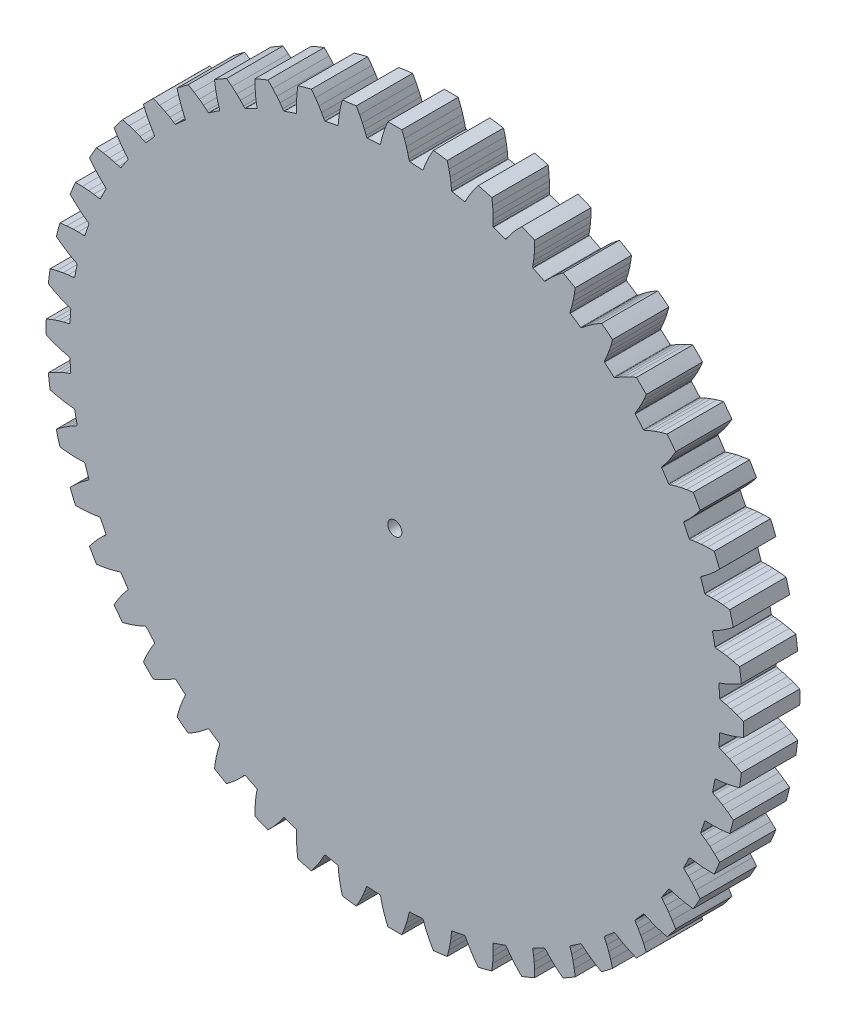
SolidWorks part; units mm, degrees
ref_plane "Front Plane" through (0, 0, 0) normal (0, 0, 1) x (1, 0, 0)
ref_plane "Top Plane" through (0, 0, 0) normal (0, 1, 0) x (1, 0, 0)
ref_plane "Right Plane" through (0, 0, 0) normal (1, 0, 0) x (0, 0, -1)
sketch "Model" plane through (0, 0, 0) normal (0, 0, 1) x (1, 0, 0)
  arc A1 (73.1624, -4.7953) -> (73.2402, -3.407) centre (0, 0) ccw
  arc A2 (73.3085, -3.2954) -> (73.2402, -3.407) centre (73.3759, -3.4133) ccw
  arc A3 (73.6777, -3.1568) -> (73.3085, -3.2954) centre (73.9216, -4.3677) ccw
  arc A4 (73.6777, -3.1568) -> (74.6891, -2.9242) centre (69.9256, 15.4758) ccw
  arc A5 (74.6891, -2.9242) -> (75.8094, -2.6049) centre (68.6862, 20.2629) ccw
  arc A6 (75.8094, -2.6049) -> (77.1527, -2.1465) centre (67.9681, 22.5684) ccw
  arc A7 (77.1527, -2.1465) -> (78.5886, -1.5721) centre (66.2481, 27.1967) ccw
  arc A8 (78.5886, -1.5721) -> (78.5886, 1.5721) centre (0, 0) ccw
  arc A9 (78.5886, 1.5721) -> (77.1527, 2.1465) centre (66.2481, -27.1967) ccw
  arc A10 (77.1527, 2.1465) -> (75.8094, 2.6049) centre (67.9681, -22.5684) ccw
  arc A11 (75.8094, 2.6049) -> (74.6891, 2.9242) centre (68.6862, -20.2629) ccw
  arc A12 (74.6891, 2.9242) -> (73.6777, 3.1568) centre (69.9256, -15.4758) ccw
  arc A13 (73.3085, 3.2954) -> (73.6777, 3.1568) centre (73.9216, 4.3677) ccw
  arc A14 (73.2402, 3.407) -> (73.3085, 3.2954) centre (73.3759, 3.4133) ccw
  arc A15 (73.2402, 3.407) -> (73.0583, 6.182) centre (0, 0) ccw
  arc A16 (73.1114, 6.3015) -> (73.0583, 6.182) centre (73.1936, 6.1934) ccw
  arc A17 (73.4595, 6.4871) -> (73.1114, 6.3015) centre (73.8593, 5.3183) ccw
  arc A18 (73.4595, 6.4871) -> (74.4318, 6.8497) centre (67.3074, 24.4705) ccw
  arc A19 (74.4318, 6.8497) -> (75.5009, 7.3125) centre (65.4538, 29.0549) ccw
  arc A20 (75.5009, 7.3125) -> (76.7728, 7.9423) centre (64.4408, 31.247) ccw
  arc A21 (76.7728, 7.9423) -> (78.1215, 8.6992) centre (62.1315, 35.6111) ccw
  arc A22 (78.1215, 8.6992) -> (77.7111, 11.8166) centre (0, 0) ccw
  arc A23 (77.7111, 11.8166) -> (76.2124, 12.1986) centre (69.2312, -18.3169) ccw
  arc A24 (76.2124, 12.1986) -> (74.8208, 12.4778) centre (70.3324, -13.5037) ccw
  arc A25 (74.8208, 12.4778) -> (73.6684, 12.6481) centre (70.7435, -11.1242) ccw
  arc A26 (73.6684, 12.6481) -> (72.6354, 12.7467) centre (71.3473, -6.2162) ccw
  arc A27 (72.2512, 12.8359) -> (72.6354, 12.7467) centre (72.7191, 13.9791) ccw
  arc A28 (72.169, 12.9376) -> (72.2512, 12.8359) centre (72.3026, 12.9615) ccw
  arc A29 (72.169, 12.9376) -> (71.6264, 15.6651) centre (0, 0) ccw
  arc A30 (71.6634, 15.7905) -> (71.6264, 15.6651) centre (71.759, 15.6941) ccw
  arc A31 (71.9843, 16.02) -> (71.6634, 15.7905) centre (72.5332, 14.9134) ccw
  arc A32 (71.9843, 16.02) -> (72.901, 16.5064) centre (63.5375, 33.0465) ccw
  arc A33 (72.901, 16.5064) -> (73.9005, 17.1047) centre (61.1014, 37.3497) ccw
  arc A34 (73.9005, 17.1047) -> (75.0793, 17.8952) centre (59.811, 39.3909) ccw
  arc A35 (75.0793, 17.8952) -> (76.3177, 18.8217) centre (56.9517, 43.4163) ccw
  arc A36 (76.3177, 18.8217) -> (75.5039, 21.8588) centre (0, 0) ccw
  arc A37 (75.5039, 21.8588) -> (73.9682, 22.0419) centre (71.0298, -9.1237) ccw
  arc A38 (73.9682, 22.0419) -> (72.5521, 22.1371) centre (71.4933, -4.208) ccw
  arc A39 (72.5521, 22.1371) -> (71.3873, 22.1556) centre (71.5902, -1.7951) ccw
  arc A40 (71.3873, 22.1556) -> (70.3502, 22.1184) centre (71.5483, 3.1496) ccw
  arc A41 (69.9576, 22.1567) -> (70.3502, 22.1184) centre (70.2723, 23.3512) ccw
  arc A42 (69.8628, 22.2468) -> (69.9576, 22.1567) centre (69.9922, 22.288) ccw
  arc A43 (69.8628, 22.2468) -> (68.9689, 24.8802) centre (0, 0) ccw
  arc A44 (68.9893, 25.0094) -> (68.9689, 24.8802) centre (69.0966, 24.9263) ccw
  arc A45 (69.2774, 25.2788) -> (68.9893, 25.0094) centre (69.9661, 24.2533) ccw
  arc A46 (69.2774, 25.2788) -> (70.1228, 25.8806) centre (58.6805, 41.0571) ccw
  arc A47 (70.1228, 25.8806) -> (71.0356, 26.6044) centre (55.7035, 45.0055) ccw
  arc A48 (71.0356, 26.6044) -> (72.1012, 27.5419) centre (54.1578, 46.8608) ccw
  arc A49 (72.1012, 27.5419) -> (73.208, 28.6221) centre (50.7976, 50.4785) ccw
  arc A50 (73.208, 28.6221) -> (72.0048, 31.527) centre (0, 0) ccw
  arc A51 (72.0048, 31.527) -> (70.4583, 31.5082) centre (71.613, 0.2256) ccw
  arc A52 (70.4583, 31.5082) -> (69.0419, 31.4176) centre (71.4309, 5.1597) ccw
  arc A53 (69.0419, 31.4176) -> (67.8847, 31.2839) centre (71.2121, 7.5646) ccw
  arc A54 (67.8847, 31.2839) -> (66.8613, 31.1117) centre (70.5251, 12.4616) ccw
  arc A55 (66.4671, 31.0985) -> (66.8613, 31.1117) centre (66.6232, 32.3238) ccw
  arc A56 (66.3614, 31.1754) -> (66.4671, 31.0985) centre (66.4843, 31.2332) ccw
  arc A57 (66.3614, 31.1754) -> (65.1314, 33.6696) centre (0, 0) ccw
  arc A58 (65.1347, 33.8003) -> (65.1314, 33.6696) centre (65.252, 33.732) ccw
  arc A59 (65.3852, 34.105) -> (65.1347, 33.8003) centre (66.2018, 33.1782) ccw
  arc A60 (65.3852, 34.105) -> (66.1448, 34.8121) centre (52.8194, 48.3652) ccw
  arc A61 (66.1448, 34.8121) -> (66.9553, 35.6488) centre (49.3526, 51.8913) ccw
  arc A62 (66.9553, 35.6488) -> (67.8894, 36.7174) centre (47.5779, 53.5289) ccw
  arc A63 (67.8894, 36.7174) -> (68.8458, 37.9328) centre (43.7742, 56.6771) ccw
  arc A64 (68.8458, 37.9328) -> (67.2737, 40.6558) centre (0, 0) ccw
  arc A65 (67.2737, 40.6558) -> (65.7429, 40.4353) centre (70.9709, 9.571) ccw
  arc A66 (65.7429, 40.4353) -> (64.3504, 40.1606) centre (70.1463, 14.4392) ccw
  arc A67 (64.3504, 40.1606) -> (63.2205, 39.877) centre (69.6155, 16.795) ccw
  arc A68 (63.2205, 39.877) -> (62.2284, 39.5727) centre (68.2952, 21.5604) ccw
  arc A69 (61.8393, 39.5081) -> (62.2284, 39.5727) centre (61.8341, 40.7434) ccw
  arc A70 (61.7244, 39.5706) -> (61.8393, 39.5081) centre (61.8387, 39.6439) ccw
  arc A71 (61.7244, 39.5706) -> (60.1794, 41.8829) centre (0, 0) ccw
  arc A72 (60.1656, 42.0129) -> (60.1794, 41.8829) centre (60.2908, 41.9605) ccw
  arc A73 (60.3742, 42.3477) -> (60.1656, 42.0129) centre (61.3049, 41.5355) ccw
  arc A74 (60.3742, 42.3477) -> (61.035, 43.1479) centre (46.0546, 54.8457) ccw
  arc A75 (61.035, 43.1479) -> (61.7294, 44.0832) centre (42.1572, 57.8892) ccw
  arc A76 (61.7294, 44.0832) -> (62.516, 45.2646) centre (40.1839, 59.2811) ccw
  arc A77 (62.516, 45.2646) -> (63.3056, 46.5945) centre (36.0019, 61.9059) ccw
  arc A78 (63.3056, 46.5945) -> (61.3915, 49.089) centre (0, 0) ccw
  arc A79 (61.3915, 49.089) -> (59.9026, 48.6705) centre (69.1145, 18.7527) ccw
  arc A80 (59.9026, 48.6705) -> (58.5579, 48.2165) centre (67.6615, 23.4716) ccw
  arc A81 (58.5579, 48.2165) -> (57.4747, 47.7878) centre (66.8277, 25.7379) ccw
  arc A82 (57.4747, 47.7878) -> (56.5307, 47.3566) centre (64.8967, 30.2902) ccw
  arc A83 (56.1534, 47.2418) -> (56.5307, 47.3566) centre (55.987, 48.4658) ccw
  arc A84 (56.0314, 47.2887) -> (56.1534, 47.2418) centre (56.1351, 47.3763) ccw
  arc A85 (56.0314, 47.2887) -> (54.1977, 49.3796) centre (0, 0) ccw
  arc A86 (54.1671, 49.5067) -> (54.1977, 49.3796) centre (54.2981, 49.471) ccw
  arc A87 (54.3302, 49.8658) -> (54.1671, 49.5067) centre (55.3589, 49.182) ccw
  arc A88 (54.3302, 49.8658) -> (54.8809, 50.7454) centre (38.5018, 60.3879) ccw
  arc A89 (54.8809, 50.7454) -> (55.4473, 51.7634) centre (34.2405, 62.8965) ccw
  arc A90 (55.4473, 51.7634) -> (56.073, 53.0374) centre (32.1024, 64.019) ccw
  arc A91 (56.073, 53.0374) -> (56.6822, 54.4589) centre (27.6135, 66.0755) ccw
  arc A92 (56.6822, 54.4589) -> (54.4589, 56.6822) centre (0, 0) ccw
  arc A93 (54.4589, 56.6822) -> (53.0374, 56.073) centre (66.0755, 27.6135) ccw
  arc A94 (53.0374, 56.073) -> (51.7634, 55.4473) centre (64.019, 32.1024) ccw
  arc A95 (51.7634, 55.4473) -> (50.7454, 54.8809) centre (62.8965, 34.2405) ccw
  arc A96 (50.7454, 54.8809) -> (49.8658, 54.3302) centre (60.3879, 38.5018) ccw
  arc A97 (49.5067, 54.1671) -> (49.8658, 54.3302) centre (49.182, 55.3589) ccw
  arc A98 (49.3796, 54.1977) -> (49.5067, 54.1671) centre (49.471, 54.2981) ccw
  arc A99 (49.3796, 54.1977) -> (47.2887, 56.0314) centre (0, 0) ccw
  arc A100 (47.2418, 56.1534) -> (47.2887, 56.0314) centre (47.3763, 56.1351) ccw
  arc A101 (47.3566, 56.5307) -> (47.2418, 56.1534) centre (48.4658, 55.987) ccw
  arc A102 (47.3566, 56.5307) -> (47.7878, 57.4747) centre (30.2902, 64.8967) ccw
  arc A103 (47.7878, 57.4747) -> (48.2165, 58.5579) centre (25.7379, 66.8277) ccw
  arc A104 (48.2165, 58.5579) -> (48.6705, 59.9026) centre (23.4716, 67.6615) ccw
  arc A105 (48.6705, 59.9026) -> (49.089, 61.3915) centre (18.7527, 69.1145) ccw
  arc A106 (49.089, 61.3915) -> (46.5945, 63.3056) centre (0, 0) ccw
  arc A107 (46.5945, 63.3056) -> (45.2646, 62.516) centre (61.9059, 36.0019) ccw
  arc A108 (45.2646, 62.516) -> (44.0832, 61.7294) centre (59.2811, 40.1839) ccw
  arc A109 (44.0832, 61.7294) -> (43.1479, 61.035) centre (57.8892, 42.1572) ccw
  arc A110 (43.1479, 61.035) -> (42.3477, 60.3742) centre (54.8457, 46.0546) ccw
  arc A111 (42.0129, 60.1656) -> (42.3477, 60.3742) centre (41.5355, 61.3049) ccw
  arc A112 (41.8829, 60.1794) -> (42.0129, 60.1656) centre (41.9605, 60.2908) ccw
  arc A113 (41.8829, 60.1794) -> (39.5706, 61.7244) centre (0, 0) ccw
  arc A114 (39.5081, 61.8393) -> (39.5706, 61.7244) centre (39.6439, 61.8387) ccw
  arc A115 (39.5727, 62.2284) -> (39.5081, 61.8393) centre (40.7434, 61.8341) ccw
  arc A116 (39.5727, 62.2284) -> (39.877, 63.2205) centre (21.5604, 68.2952) ccw
  arc A117 (39.877, 63.2205) -> (40.1606, 64.3504) centre (16.795, 69.6155) ccw
  arc A118 (40.1606, 64.3504) -> (40.4353, 65.7429) centre (14.4392, 70.1463) ccw
  arc A119 (40.4353, 65.7429) -> (40.6558, 67.2737) centre (9.571, 70.9709) ccw
  arc A120 (40.6558, 67.2737) -> (37.9328, 68.8458) centre (0, 0) ccw
  arc A121 (37.9328, 68.8458) -> (36.7174, 67.8894) centre (56.6771, 43.7742) ccw
  arc A122 (36.7174, 67.8894) -> (35.6488, 66.9553) centre (53.5289, 47.5779) ccw
  arc A123 (35.6488, 66.9553) -> (34.8121, 66.1448) centre (51.8913, 49.3526) ccw
  arc A124 (34.8121, 66.1448) -> (34.105, 65.3852) centre (48.3652, 52.8194) ccw
  arc A125 (33.8003, 65.1347) -> (34.105, 65.3852) centre (33.1782, 66.2018) ccw
  arc A126 (33.6696, 65.1314) -> (33.8003, 65.1347) centre (33.732, 65.252) ccw
  arc A127 (33.6696, 65.1314) -> (31.1754, 66.3614) centre (0, 0) ccw
  arc A128 (31.0985, 66.4671) -> (31.1754, 66.3614) centre (31.2332, 66.4843) ccw
  arc A129 (31.1117, 66.8613) -> (31.0985, 66.4671) centre (32.3238, 66.6232) ccw
  arc A130 (31.1117, 66.8613) -> (31.2839, 67.8847) centre (12.4616, 70.5251) ccw
  arc A131 (31.2839, 67.8847) -> (31.4176, 69.0419) centre (7.5646, 71.2121) ccw
  arc A132 (31.4176, 69.0419) -> (31.5082, 70.4583) centre (5.1597, 71.4309) ccw
  arc A133 (31.5082, 70.4583) -> (31.527, 72.0048) centre (0.2256, 71.613) ccw
  arc A134 (31.527, 72.0048) -> (28.6221, 73.208) centre (0, 0) ccw
  arc A135 (28.6221, 73.208) -> (27.5419, 72.1012) centre (50.4785, 50.7976) ccw
  arc A136 (27.5419, 72.1012) -> (26.6044, 71.0356) centre (46.8608, 54.1578) ccw
  arc A137 (26.6044, 71.0356) -> (25.8806, 70.1228) centre (45.0055, 55.7035) ccw
  arc A138 (25.8806, 70.1228) -> (25.2788, 69.2774) centre (41.0571, 58.6805) ccw
  arc A139 (25.0094, 68.9893) -> (25.2788, 69.2774) centre (24.2533, 69.9661) ccw
  arc A140 (24.8802, 68.9689) -> (25.0094, 68.9893) centre (24.9263, 69.0966) ccw
  arc A141 (24.8802, 68.9689) -> (22.2468, 69.8628) centre (0, 0) ccw
  arc A142 (22.1567, 69.9576) -> (22.2468, 69.8628) centre (22.288, 69.9922) ccw
  arc A143 (22.1184, 70.3502) -> (22.1567, 69.9576) centre (23.3512, 70.2723) ccw
  arc A144 (22.1184, 70.3502) -> (22.1556, 71.3873) centre (3.1496, 71.5483) ccw
  arc A145 (22.1556, 71.3873) -> (22.1371, 72.5521) centre (-1.7951, 71.5902) ccw
  arc A146 (22.1371, 72.5521) -> (22.0419, 73.9682) centre (-4.208, 71.4933) ccw
  arc A147 (22.0419, 73.9682) -> (21.8588, 75.5039) centre (-9.1237, 71.0298) ccw
  arc A148 (21.8588, 75.5039) -> (18.8217, 76.3177) centre (0, 0) ccw
  arc A149 (18.8217, 76.3177) -> (17.8952, 75.0793) centre (43.4163, 56.9517) ccw
  arc A150 (17.8952, 75.0793) -> (17.1047, 73.9005) centre (39.3909, 59.811) ccw
  arc A151 (17.1047, 73.9005) -> (16.5064, 72.901) centre (37.3497, 61.1014) ccw
  arc A152 (16.5064, 72.901) -> (16.02, 71.9843) centre (33.0465, 63.5375) ccw
  arc A153 (15.7905, 71.6634) -> (16.02, 71.9843) centre (14.9134, 72.5332) ccw
  arc A154 (15.6651, 71.6264) -> (15.7905, 71.6634) centre (15.6941, 71.759) ccw
  arc A155 (15.6651, 71.6264) -> (12.9376, 72.169) centre (0, 0) ccw
  arc A156 (12.8359, 72.2512) -> (12.9376, 72.169) centre (12.9615, 72.3026) ccw
  arc A157 (12.7467, 72.6354) -> (12.8359, 72.2512) centre (13.9791, 72.7191) ccw
  arc A158 (12.7467, 72.6354) -> (12.6481, 73.6684) centre (-6.2162, 71.3473) ccw
  arc A159 (12.6481, 73.6684) -> (12.4778, 74.8208) centre (-11.1242, 70.7435) ccw
  arc A160 (12.4778, 74.8208) -> (12.1986, 76.2124) centre (-13.5037, 70.3324) ccw
  arc A161 (12.1986, 76.2124) -> (11.8166, 77.7111) centre (-18.3169, 69.2312) ccw
  arc A162 (11.8166, 77.7111) -> (8.6992, 78.1215) centre (0, 0) ccw
  arc A163 (8.6992, 78.1215) -> (7.9423, 76.7728) centre (35.6111, 62.1315) ccw
  arc A164 (7.9423, 76.7728) -> (7.3125, 75.5009) centre (31.247, 64.4408) ccw
  arc A165 (7.3125, 75.5009) -> (6.8497, 74.4318) centre (29.0549, 65.4538) ccw
  arc A166 (6.8497, 74.4318) -> (6.4871, 73.4595) centre (24.4705, 67.3074) ccw
  arc A167 (6.3015, 73.1114) -> (6.4871, 73.4595) centre (5.3183, 73.8593) ccw
  arc A168 (6.182, 73.0583) -> (6.3015, 73.1114) centre (6.1934, 73.1936) ccw
  arc A169 (6.182, 73.0583) -> (3.407, 73.2402) centre (0, 0) ccw
  arc A170 (3.2954, 73.3085) -> (3.407, 73.2402) centre (3.4133, 73.3759) ccw
  arc A171 (3.1568, 73.6777) -> (3.2954, 73.3085) centre (4.3677, 73.9216) ccw
  arc A172 (3.1568, 73.6777) -> (2.9242, 74.6891) centre (-15.4758, 69.9256) ccw
  arc A173 (2.9242, 74.6891) -> (2.6049, 75.8094) centre (-20.2629, 68.6862) ccw
  arc A174 (2.6049, 75.8094) -> (2.1465, 77.1527) centre (-22.5684, 67.9681) ccw
  arc A175 (2.1465, 77.1527) -> (1.5721, 78.5886) centre (-27.1967, 66.2481) ccw
  arc A176 (1.5721, 78.5886) -> (-1.5721, 78.5886) centre (0, 0) ccw
  arc A177 (-1.5721, 78.5886) -> (-2.1465, 77.1527) centre (27.1967, 66.2481) ccw
  arc A178 (-2.1465, 77.1527) -> (-2.6049, 75.8094) centre (22.5684, 67.9681) ccw
  arc A179 (-2.6049, 75.8094) -> (-2.9242, 74.6891) centre (20.2629, 68.6862) ccw
  arc A180 (-2.9242, 74.6891) -> (-3.1568, 73.6777) centre (15.4758, 69.9256) ccw
  arc A181 (-3.2954, 73.3085) -> (-3.1568, 73.6777) centre (-4.3677, 73.9216) ccw
  arc A182 (-3.407, 73.2402) -> (-3.2954, 73.3085) centre (-3.4133, 73.3759) ccw
  arc A183 (-3.407, 73.2402) -> (-6.182, 73.0583) centre (0, 0) ccw
  arc A184 (-6.3015, 73.1114) -> (-6.182, 73.0583) centre (-6.1934, 73.1936) ccw
  arc A185 (-6.4871, 73.4595) -> (-6.3015, 73.1114) centre (-5.3183, 73.8593) ccw
  arc A186 (-6.4871, 73.4595) -> (-6.8497, 74.4318) centre (-24.4705, 67.3074) ccw
  arc A187 (-6.8497, 74.4318) -> (-7.3125, 75.5009) centre (-29.0549, 65.4538) ccw
  arc A188 (-7.3125, 75.5009) -> (-7.9423, 76.7728) centre (-31.247, 64.4408) ccw
  arc A189 (-7.9423, 76.7728) -> (-8.6992, 78.1215) centre (-35.6111, 62.1315) ccw
  arc A190 (-8.6992, 78.1215) -> (-11.8166, 77.7111) centre (0, 0) ccw
  arc A191 (-11.8166, 77.7111) -> (-12.1986, 76.2124) centre (18.3169, 69.2312) ccw
  arc A192 (-12.1986, 76.2124) -> (-12.4778, 74.8208) centre (13.5037, 70.3324) ccw
  arc A193 (-12.4778, 74.8208) -> (-12.6481, 73.6684) centre (11.1242, 70.7435) ccw
  arc A194 (-12.6481, 73.6684) -> (-12.7467, 72.6354) centre (6.2162, 71.3473) ccw
  arc A195 (-12.8359, 72.2512) -> (-12.7467, 72.6354) centre (-13.9791, 72.7191) ccw
  arc A196 (-12.9376, 72.169) -> (-12.8359, 72.2512) centre (-12.9615, 72.3026) ccw
  arc A197 (-12.9376, 72.169) -> (-15.6651, 71.6264) centre (0, 0) ccw
  arc A198 (-15.7905, 71.6634) -> (-15.6651, 71.6264) centre (-15.6941, 71.759) ccw
  arc A199 (-16.02, 71.9843) -> (-15.7905, 71.6634) centre (-14.9134, 72.5332) ccw
  arc A200 (-16.02, 71.9843) -> (-16.5064, 72.901) centre (-33.0465, 63.5375) ccw
  arc A201 (-16.5064, 72.901) -> (-17.1047, 73.9005) centre (-37.3497, 61.1014) ccw
  arc A202 (-17.1047, 73.9005) -> (-17.8952, 75.0793) centre (-39.3909, 59.811) ccw
  arc A203 (-17.8952, 75.0793) -> (-18.8217, 76.3177) centre (-43.4163, 56.9517) ccw
  arc A204 (-18.8217, 76.3177) -> (-21.8588, 75.5039) centre (0, 0) ccw
  arc A205 (-21.8588, 75.5039) -> (-22.0419, 73.9682) centre (9.1237, 71.0298) ccw
  arc A206 (-22.0419, 73.9682) -> (-22.1371, 72.5521) centre (4.208, 71.4933) ccw
  arc A207 (-22.1371, 72.5521) -> (-22.1556, 71.3873) centre (1.7951, 71.5902) ccw
  arc A208 (-22.1556, 71.3873) -> (-22.1184, 70.3502) centre (-3.1496, 71.5483) ccw
  arc A209 (-22.1567, 69.9576) -> (-22.1184, 70.3502) centre (-23.3512, 70.2723) ccw
  arc A210 (-22.2468, 69.8628) -> (-22.1567, 69.9576) centre (-22.288, 69.9922) ccw
  arc A211 (-22.2468, 69.8628) -> (-24.8802, 68.9689) centre (0, 0) ccw
  arc A212 (-25.0094, 68.9893) -> (-24.8802, 68.9689) centre (-24.9263, 69.0966) ccw
  arc A213 (-25.2788, 69.2774) -> (-25.0094, 68.9893) centre (-24.2533, 69.9661) ccw
  arc A214 (-25.2788, 69.2774) -> (-25.8806, 70.1228) centre (-41.0571, 58.6805) ccw
  arc A215 (-25.8806, 70.1228) -> (-26.6044, 71.0356) centre (-45.0055, 55.7035) ccw
  arc A216 (-26.6044, 71.0356) -> (-27.5419, 72.1012) centre (-46.8608, 54.1578) ccw
  arc A217 (-27.5419, 72.1012) -> (-28.6221, 73.208) centre (-50.4785, 50.7976) ccw
  arc A218 (-28.6221, 73.208) -> (-31.527, 72.0048) centre (0, 0) ccw
  arc A219 (-31.527, 72.0048) -> (-31.5082, 70.4583) centre (-0.2256, 71.613) ccw
  arc A220 (-31.5082, 70.4583) -> (-31.4176, 69.0419) centre (-5.1597, 71.4309) ccw
  arc A221 (-31.4176, 69.0419) -> (-31.2839, 67.8847) centre (-7.5646, 71.2121) ccw
  arc A222 (-31.2839, 67.8847) -> (-31.1117, 66.8613) centre (-12.4616, 70.5251) ccw
  arc A223 (-31.0985, 66.4671) -> (-31.1117, 66.8613) centre (-32.3238, 66.6232) ccw
  arc A224 (-31.1754, 66.3614) -> (-31.0985, 66.4671) centre (-31.2332, 66.4843) ccw
  arc A225 (-31.1754, 66.3614) -> (-33.6696, 65.1314) centre (0, 0) ccw
  arc A226 (-33.8003, 65.1347) -> (-33.6696, 65.1314) centre (-33.732, 65.252) ccw
  arc A227 (-34.105, 65.3852) -> (-33.8003, 65.1347) centre (-33.1782, 66.2018) ccw
  arc A228 (-34.105, 65.3852) -> (-34.8121, 66.1448) centre (-48.3652, 52.8194) ccw
  arc A229 (-34.8121, 66.1448) -> (-35.6488, 66.9553) centre (-51.8913, 49.3526) ccw
  arc A230 (-35.6488, 66.9553) -> (-36.7174, 67.8894) centre (-53.5289, 47.5779) ccw
  arc A231 (-36.7174, 67.8894) -> (-37.9328, 68.8458) centre (-56.6771, 43.7742) ccw
  arc A232 (-37.9328, 68.8458) -> (-40.6558, 67.2737) centre (0, 0) ccw
  arc A233 (-40.6558, 67.2737) -> (-40.4353, 65.7429) centre (-9.571, 70.9709) ccw
  arc A234 (-40.4353, 65.7429) -> (-40.1606, 64.3504) centre (-14.4392, 70.1463) ccw
  arc A235 (-40.1606, 64.3504) -> (-39.877, 63.2205) centre (-16.795, 69.6155) ccw
  arc A236 (-39.877, 63.2205) -> (-39.5727, 62.2284) centre (-21.5604, 68.2952) ccw
  arc A237 (-39.5081, 61.8393) -> (-39.5727, 62.2284) centre (-40.7434, 61.8341) ccw
  arc A238 (-39.5706, 61.7244) -> (-39.5081, 61.8393) centre (-39.6439, 61.8387) ccw
  arc A239 (-39.5706, 61.7244) -> (-41.8829, 60.1794) centre (0, 0) ccw
  arc A240 (-42.0129, 60.1656) -> (-41.8829, 60.1794) centre (-41.9605, 60.2908) ccw
  arc A241 (-42.3477, 60.3742) -> (-42.0129, 60.1656) centre (-41.5355, 61.3049) ccw
  arc A242 (-42.3477, 60.3742) -> (-43.1479, 61.035) centre (-54.8457, 46.0546) ccw
  arc A243 (-43.1479, 61.035) -> (-44.0832, 61.7294) centre (-57.8892, 42.1572) ccw
  arc A244 (-44.0832, 61.7294) -> (-45.2646, 62.516) centre (-59.2811, 40.1839) ccw
  arc A245 (-45.2646, 62.516) -> (-46.5945, 63.3056) centre (-61.9059, 36.0019) ccw
  arc A246 (-46.5945, 63.3056) -> (-49.089, 61.3915) centre (0, 0) ccw
  arc A247 (-49.089, 61.3915) -> (-48.6705, 59.9026) centre (-18.7527, 69.1145) ccw
  arc A248 (-48.6705, 59.9026) -> (-48.2165, 58.5579) centre (-23.4716, 67.6615) ccw
  arc A249 (-48.2165, 58.5579) -> (-47.7878, 57.4747) centre (-25.7379, 66.8277) ccw
  arc A250 (-47.7878, 57.4747) -> (-47.3566, 56.5307) centre (-30.2902, 64.8967) ccw
  arc A251 (-47.2418, 56.1534) -> (-47.3566, 56.5307) centre (-48.4658, 55.987) ccw
  arc A252 (-47.2887, 56.0314) -> (-47.2418, 56.1534) centre (-47.3763, 56.1351) ccw
  arc A253 (-47.2887, 56.0314) -> (-49.3796, 54.1977) centre (0, 0) ccw
  arc A254 (-49.5067, 54.1671) -> (-49.3796, 54.1977) centre (-49.471, 54.2981) ccw
  arc A255 (-49.8658, 54.3302) -> (-49.5067, 54.1671) centre (-49.182, 55.3589) ccw
  arc A256 (-49.8658, 54.3302) -> (-50.7454, 54.8809) centre (-60.3879, 38.5018) ccw
  arc A257 (-50.7454, 54.8809) -> (-51.7634, 55.4473) centre (-62.8965, 34.2405) ccw
  arc A258 (-51.7634, 55.4473) -> (-53.0374, 56.073) centre (-64.019, 32.1024) ccw
  arc A259 (-53.0374, 56.073) -> (-54.4589, 56.6822) centre (-66.0755, 27.6135) ccw
  arc A260 (-54.4589, 56.6822) -> (-56.6822, 54.4589) centre (0, 0) ccw
  arc A261 (-56.6822, 54.4589) -> (-56.073, 53.0374) centre (-27.6135, 66.0755) ccw
  arc A262 (-56.073, 53.0374) -> (-55.4473, 51.7634) centre (-32.1024, 64.019) ccw
  arc A263 (-55.4473, 51.7634) -> (-54.8809, 50.7454) centre (-34.2405, 62.8965) ccw
  arc A264 (-54.8809, 50.7454) -> (-54.3302, 49.8658) centre (-38.5018, 60.3879) ccw
  arc A265 (-54.1671, 49.5067) -> (-54.3302, 49.8658) centre (-55.3589, 49.182) ccw
  arc A266 (-54.1977, 49.3796) -> (-54.1671, 49.5067) centre (-54.2981, 49.471) ccw
  arc A267 (-54.1977, 49.3796) -> (-56.0314, 47.2887) centre (0, 0) ccw
  arc A268 (-56.1534, 47.2418) -> (-56.0314, 47.2887) centre (-56.1351, 47.3763) ccw
  arc A269 (-56.5307, 47.3566) -> (-56.1534, 47.2418) centre (-55.987, 48.4658) ccw
  arc A270 (-56.5307, 47.3566) -> (-57.4747, 47.7878) centre (-64.8967, 30.2902) ccw
  arc A271 (-57.4747, 47.7878) -> (-58.5579, 48.2165) centre (-66.8277, 25.7379) ccw
  arc A272 (-58.5579, 48.2165) -> (-59.9026, 48.6705) centre (-67.6615, 23.4716) ccw
  arc A273 (-59.9026, 48.6705) -> (-61.3915, 49.089) centre (-69.1145, 18.7527) ccw
  arc A274 (-61.3915, 49.089) -> (-63.3056, 46.5945) centre (0, 0) ccw
  arc A275 (-63.3056, 46.5945) -> (-62.516, 45.2646) centre (-36.0019, 61.9059) ccw
  arc A276 (-62.516, 45.2646) -> (-61.7294, 44.0832) centre (-40.1839, 59.2811) ccw
  arc A277 (-61.7294, 44.0832) -> (-61.035, 43.1479) centre (-42.1572, 57.8892) ccw
  arc A278 (-61.035, 43.1479) -> (-60.3742, 42.3477) centre (-46.0546, 54.8457) ccw
  arc A279 (-60.1656, 42.0129) -> (-60.3742, 42.3477) centre (-61.3049, 41.5355) ccw
  arc A280 (-60.1794, 41.8829) -> (-60.1656, 42.0129) centre (-60.2908, 41.9605) ccw
  arc A281 (-60.1794, 41.8829) -> (-61.7244, 39.5706) centre (0, 0) ccw
  arc A282 (-61.8393, 39.5081) -> (-61.7244, 39.5706) centre (-61.8387, 39.6439) ccw
  arc A283 (-62.2284, 39.5727) -> (-61.8393, 39.5081) centre (-61.8341, 40.7434) ccw
  arc A284 (-62.2284, 39.5727) -> (-63.2205, 39.877) centre (-68.2952, 21.5604) ccw
  arc A285 (-63.2205, 39.877) -> (-64.3504, 40.1606) centre (-69.6155, 16.795) ccw
  arc A286 (-64.3504, 40.1606) -> (-65.7429, 40.4353) centre (-70.1463, 14.4392) ccw
  arc A287 (-65.7429, 40.4353) -> (-67.2737, 40.6558) centre (-70.9709, 9.571) ccw
  arc A288 (-67.2737, 40.6558) -> (-68.8458, 37.9328) centre (0, 0) ccw
  arc A289 (-68.8458, 37.9328) -> (-67.8894, 36.7174) centre (-43.7742, 56.6771) ccw
  arc A290 (-67.8894, 36.7174) -> (-66.9553, 35.6488) centre (-47.5779, 53.5289) ccw
  arc A291 (-66.9553, 35.6488) -> (-66.1448, 34.8121) centre (-49.3526, 51.8913) ccw
  arc A292 (-66.1448, 34.8121) -> (-65.3852, 34.105) centre (-52.8194, 48.3652) ccw
  arc A293 (-65.1347, 33.8003) -> (-65.3852, 34.105) centre (-66.2018, 33.1782) ccw
  arc A294 (-65.1314, 33.6696) -> (-65.1347, 33.8003) centre (-65.252, 33.732) ccw
  arc A295 (-65.1314, 33.6696) -> (-66.3614, 31.1754) centre (0, 0) ccw
  arc A296 (-66.4671, 31.0985) -> (-66.3614, 31.1754) centre (-66.4843, 31.2332) ccw
  arc A297 (-66.8613, 31.1117) -> (-66.4671, 31.0985) centre (-66.6232, 32.3238) ccw
  arc A298 (-66.8613, 31.1117) -> (-67.8847, 31.2839) centre (-70.5251, 12.4616) ccw
  arc A299 (-67.8847, 31.2839) -> (-69.0419, 31.4176) centre (-71.2121, 7.5646) ccw
  arc A300 (-69.0419, 31.4176) -> (-70.4583, 31.5082) centre (-71.4309, 5.1597) ccw
  arc A301 (-70.4583, 31.5082) -> (-72.0048, 31.527) centre (-71.613, 0.2256) ccw
  arc A302 (-72.0048, 31.527) -> (-73.208, 28.6221) centre (0, 0) ccw
  arc A303 (-73.208, 28.6221) -> (-72.1012, 27.5419) centre (-50.7976, 50.4785) ccw
  arc A304 (-72.1012, 27.5419) -> (-71.0356, 26.6044) centre (-54.1578, 46.8608) ccw
  arc A305 (-71.0356, 26.6044) -> (-70.1228, 25.8806) centre (-55.7035, 45.0055) ccw
  arc A306 (-70.1228, 25.8806) -> (-69.2774, 25.2788) centre (-58.6805, 41.0571) ccw
  arc A307 (-68.9893, 25.0094) -> (-69.2774, 25.2788) centre (-69.9661, 24.2533) ccw
  arc A308 (-68.9689, 24.8802) -> (-68.9893, 25.0094) centre (-69.0966, 24.9263) ccw
  arc A309 (-68.9689, 24.8802) -> (-69.8628, 22.2468) centre (0, 0) ccw
  arc A310 (-69.9576, 22.1567) -> (-69.8628, 22.2468) centre (-69.9922, 22.288) ccw
  arc A311 (-70.3502, 22.1184) -> (-69.9576, 22.1567) centre (-70.2723, 23.3512) ccw
  arc A312 (-70.3502, 22.1184) -> (-71.3873, 22.1556) centre (-71.5483, 3.1496) ccw
  arc A313 (-71.3873, 22.1556) -> (-72.5521, 22.1371) centre (-71.5902, -1.7951) ccw
  arc A314 (-72.5521, 22.1371) -> (-73.9682, 22.0419) centre (-71.4933, -4.208) ccw
  arc A315 (-73.9682, 22.0419) -> (-75.5039, 21.8588) centre (-71.0298, -9.1237) ccw
  arc A316 (-75.5039, 21.8588) -> (-76.3177, 18.8217) centre (0, 0) ccw
  arc A317 (-76.3177, 18.8217) -> (-75.0793, 17.8952) centre (-56.9517, 43.4163) ccw
  arc A318 (-75.0793, 17.8952) -> (-73.9005, 17.1047) centre (-59.811, 39.3909) ccw
  arc A319 (-73.9005, 17.1047) -> (-72.901, 16.5064) centre (-61.1014, 37.3497) ccw
  arc A320 (-72.901, 16.5064) -> (-71.9843, 16.02) centre (-63.5375, 33.0465) ccw
  arc A321 (-71.6634, 15.7905) -> (-71.9843, 16.02) centre (-72.5332, 14.9134) ccw
  arc A322 (-71.6264, 15.6651) -> (-71.6634, 15.7905) centre (-71.759, 15.6941) ccw
  arc A323 (-71.6264, 15.6651) -> (-72.169, 12.9376) centre (0, 0) ccw
  arc A324 (-72.2512, 12.8359) -> (-72.169, 12.9376) centre (-72.3026, 12.9615) ccw
  arc A325 (-72.6354, 12.7467) -> (-72.2512, 12.8359) centre (-72.7191, 13.9791) ccw
  arc A326 (-72.6354, 12.7467) -> (-73.6684, 12.6481) centre (-71.3473, -6.2162) ccw
  arc A327 (-73.6684, 12.6481) -> (-74.8208, 12.4778) centre (-70.7435, -11.1242) ccw
  arc A328 (-74.8208, 12.4778) -> (-76.2124, 12.1986) centre (-70.3324, -13.5037) ccw
  arc A329 (-76.2124, 12.1986) -> (-77.7111, 11.8166) centre (-69.2312, -18.3169) ccw
  arc A330 (-77.7111, 11.8166) -> (-78.1215, 8.6992) centre (0, 0) ccw
  arc A331 (-78.1215, 8.6992) -> (-76.7728, 7.9423) centre (-62.1315, 35.6111) ccw
  arc A332 (-76.7728, 7.9423) -> (-75.5009, 7.3125) centre (-64.4408, 31.247) ccw
  arc A333 (-75.5009, 7.3125) -> (-74.4318, 6.8497) centre (-65.4538, 29.0549) ccw
  arc A334 (-74.4318, 6.8497) -> (-73.4595, 6.4871) centre (-67.3074, 24.4705) ccw
  arc A335 (-73.1114, 6.3015) -> (-73.4595, 6.4871) centre (-73.8593, 5.3183) ccw
  arc A336 (-73.0583, 6.182) -> (-73.1114, 6.3015) centre (-73.1936, 6.1934) ccw
  arc A337 (-73.0583, 6.182) -> (-73.2402, 3.407) centre (0, 0) ccw
  arc A338 (-73.3085, 3.2954) -> (-73.2402, 3.407) centre (-73.3759, 3.4133) ccw
  arc A339 (-73.6777, 3.1568) -> (-73.3085, 3.2954) centre (-73.9216, 4.3677) ccw
  arc A340 (-73.6777, 3.1568) -> (-74.6891, 2.9242) centre (-69.9256, -15.4758) ccw
  arc A341 (-74.6891, 2.9242) -> (-75.8094, 2.6049) centre (-68.6862, -20.2629) ccw
  arc A342 (-75.8094, 2.6049) -> (-77.1527, 2.1465) centre (-67.9681, -22.5684) ccw
  arc A343 (-77.1527, 2.1465) -> (-78.5886, 1.5721) centre (-66.2481, -27.1967) ccw
  arc A344 (-78.5886, 1.5721) -> (-78.5886, -1.5721) centre (0, 0) ccw
  arc A345 (-78.5886, -1.5721) -> (-77.1527, -2.1465) centre (-66.2481, 27.1967) ccw
  arc A346 (-77.1527, -2.1465) -> (-75.8094, -2.6049) centre (-67.9681, 22.5684) ccw
  arc A347 (-75.8094, -2.6049) -> (-74.6891, -2.9242) centre (-68.6862, 20.2629) ccw
  arc A348 (-74.6891, -2.9242) -> (-73.6777, -3.1568) centre (-69.9256, 15.4758) ccw
  arc A349 (-73.3085, -3.2954) -> (-73.6777, -3.1568) centre (-73.9216, -4.3677) ccw
  arc A350 (-73.2402, -3.407) -> (-73.3085, -3.2954) centre (-73.3759, -3.4133) ccw
  arc A351 (-73.2402, -3.407) -> (-73.0583, -6.182) centre (0, 0) ccw
  arc A352 (-73.1114, -6.3015) -> (-73.0583, -6.182) centre (-73.1936, -6.1934) ccw
  arc A353 (-73.4595, -6.4871) -> (-73.1114, -6.3015) centre (-73.8593, -5.3183) ccw
  arc A354 (-73.4595, -6.4871) -> (-74.4318, -6.8497) centre (-67.3074, -24.4705) ccw
  arc A355 (-74.4318, -6.8497) -> (-75.5009, -7.3125) centre (-65.4538, -29.0549) ccw
  arc A356 (-75.5009, -7.3125) -> (-76.7728, -7.9423) centre (-64.4408, -31.247) ccw
  arc A357 (-76.7728, -7.9423) -> (-78.1215, -8.6992) centre (-62.1315, -35.6111) ccw
  arc A358 (-78.1215, -8.6992) -> (-77.7111, -11.8166) centre (0, 0) ccw
  arc A359 (-77.7111, -11.8166) -> (-76.2124, -12.1986) centre (-69.2312, 18.3169) ccw
  arc A360 (-76.2124, -12.1986) -> (-74.8208, -12.4778) centre (-70.3324, 13.5037) ccw
  arc A361 (-74.8208, -12.4778) -> (-73.6684, -12.6481) centre (-70.7435, 11.1242) ccw
  arc A362 (-73.6684, -12.6481) -> (-72.6354, -12.7467) centre (-71.3473, 6.2162) ccw
  arc A363 (-72.2512, -12.8359) -> (-72.6354, -12.7467) centre (-72.7191, -13.9791) ccw
  arc A364 (-72.169, -12.9376) -> (-72.2512, -12.8359) centre (-72.3026, -12.9615) ccw
  arc A365 (-72.169, -12.9376) -> (-71.6264, -15.6651) centre (0, 0) ccw
  arc A366 (-71.6634, -15.7905) -> (-71.6264, -15.6651) centre (-71.759, -15.6941) ccw
  arc A367 (-71.9843, -16.02) -> (-71.6634, -15.7905) centre (-72.5332, -14.9134) ccw
  arc A368 (-71.9843, -16.02) -> (-72.901, -16.5064) centre (-63.5375, -33.0465) ccw
  arc A369 (-72.901, -16.5064) -> (-73.9005, -17.1047) centre (-61.1014, -37.3497) ccw
  arc A370 (-73.9005, -17.1047) -> (-75.0793, -17.8952) centre (-59.811, -39.3909) ccw
  arc A371 (-75.0793, -17.8952) -> (-76.3177, -18.8217) centre (-56.9517, -43.4163) ccw
  arc A372 (-76.3177, -18.8217) -> (-75.5039, -21.8588) centre (0, 0) ccw
  arc A373 (-75.5039, -21.8588) -> (-73.9682, -22.0419) centre (-71.0298, 9.1237) ccw
  arc A374 (-73.9682, -22.0419) -> (-72.5521, -22.1371) centre (-71.4933, 4.208) ccw
  arc A375 (-72.5521, -22.1371) -> (-71.3873, -22.1556) centre (-71.5902, 1.7951) ccw
  arc A376 (-71.3873, -22.1556) -> (-70.3502, -22.1184) centre (-71.5483, -3.1496) ccw
  arc A377 (-69.9576, -22.1567) -> (-70.3502, -22.1184) centre (-70.2723, -23.3512) ccw
  arc A378 (-69.8628, -22.2468) -> (-69.9576, -22.1567) centre (-69.9922, -22.288) ccw
  arc A379 (-69.8628, -22.2468) -> (-68.9689, -24.8802) centre (0, 0) ccw
  arc A380 (-68.9893, -25.0094) -> (-68.9689, -24.8802) centre (-69.0966, -24.9263) ccw
  arc A381 (-69.2774, -25.2788) -> (-68.9893, -25.0094) centre (-69.9661, -24.2533) ccw
  arc A382 (-69.2774, -25.2788) -> (-70.1228, -25.8806) centre (-58.6805, -41.0571) ccw
  arc A383 (-70.1228, -25.8806) -> (-71.0356, -26.6044) centre (-55.7035, -45.0055) ccw
  arc A384 (-71.0356, -26.6044) -> (-72.1012, -27.5419) centre (-54.1578, -46.8608) ccw
  arc A385 (-72.1012, -27.5419) -> (-73.208, -28.6221) centre (-50.7976, -50.4785) ccw
  arc A386 (-73.208, -28.6221) -> (-72.0048, -31.527) centre (0, 0) ccw
  arc A387 (-72.0048, -31.527) -> (-70.4583, -31.5082) centre (-71.613, -0.2256) ccw
  arc A388 (-70.4583, -31.5082) -> (-69.0419, -31.4176) centre (-71.4309, -5.1597) ccw
  arc A389 (-69.0419, -31.4176) -> (-67.8847, -31.2839) centre (-71.2121, -7.5646) ccw
  arc A390 (-67.8847, -31.2839) -> (-66.8613, -31.1117) centre (-70.5251, -12.4616) ccw
  arc A391 (-66.4671, -31.0985) -> (-66.8613, -31.1117) centre (-66.6232, -32.3238) ccw
  arc A392 (-66.3614, -31.1754) -> (-66.4671, -31.0985) centre (-66.4843, -31.2332) ccw
  arc A393 (-66.3614, -31.1754) -> (-65.1314, -33.6696) centre (0, 0) ccw
  arc A394 (-65.1347, -33.8003) -> (-65.1314, -33.6696) centre (-65.252, -33.732) ccw
  arc A395 (-65.3852, -34.105) -> (-65.1347, -33.8003) centre (-66.2018, -33.1782) ccw
  arc A396 (-65.3852, -34.105) -> (-66.1448, -34.8121) centre (-52.8194, -48.3652) ccw
  arc A397 (-66.1448, -34.8121) -> (-66.9553, -35.6488) centre (-49.3526, -51.8913) ccw
  arc A398 (-66.9553, -35.6488) -> (-67.8894, -36.7174) centre (-47.5779, -53.5289) ccw
  arc A399 (-67.8894, -36.7174) -> (-68.8458, -37.9328) centre (-43.7742, -56.6771) ccw
  arc A400 (-68.8458, -37.9328) -> (-67.2737, -40.6558) centre (0, 0) ccw
  arc A401 (-67.2737, -40.6558) -> (-65.7429, -40.4353) centre (-70.9709, -9.571) ccw
  arc A402 (-65.7429, -40.4353) -> (-64.3504, -40.1606) centre (-70.1463, -14.4392) ccw
  arc A403 (-64.3504, -40.1606) -> (-63.2205, -39.877) centre (-69.6155, -16.795) ccw
  arc A404 (-63.2205, -39.877) -> (-62.2284, -39.5727) centre (-68.2952, -21.5604) ccw
  arc A405 (-61.8393, -39.5081) -> (-62.2284, -39.5727) centre (-61.8341, -40.7434) ccw
  arc A406 (-61.7244, -39.5706) -> (-61.8393, -39.5081) centre (-61.8387, -39.6439) ccw
  arc A407 (-61.7244, -39.5706) -> (-60.1794, -41.8829) centre (0, 0) ccw
  arc A408 (-60.1656, -42.0129) -> (-60.1794, -41.8829) centre (-60.2908, -41.9605) ccw
  arc A409 (-60.3742, -42.3477) -> (-60.1656, -42.0129) centre (-61.3049, -41.5355) ccw
  arc A410 (-60.3742, -42.3477) -> (-61.035, -43.1479) centre (-46.0546, -54.8457) ccw
  arc A411 (-61.035, -43.1479) -> (-61.7294, -44.0832) centre (-42.1572, -57.8892) ccw
  arc A412 (-61.7294, -44.0832) -> (-62.516, -45.2646) centre (-40.1839, -59.2811) ccw
  arc A413 (-62.516, -45.2646) -> (-63.3056, -46.5945) centre (-36.0019, -61.9059) ccw
  arc A414 (-63.3056, -46.5945) -> (-61.3915, -49.089) centre (0, 0) ccw
  arc A415 (-61.3915, -49.089) -> (-59.9026, -48.6705) centre (-69.1145, -18.7527) ccw
  arc A416 (-59.9026, -48.6705) -> (-58.5579, -48.2165) centre (-67.6615, -23.4716) ccw
  arc A417 (-58.5579, -48.2165) -> (-57.4747, -47.7878) centre (-66.8277, -25.7379) ccw
  arc A418 (-57.4747, -47.7878) -> (-56.5307, -47.3566) centre (-64.8967, -30.2902) ccw
  arc A419 (-56.1534, -47.2418) -> (-56.5307, -47.3566) centre (-55.987, -48.4658) ccw
  arc A420 (-56.0314, -47.2887) -> (-56.1534, -47.2418) centre (-56.1351, -47.3763) ccw
  arc A421 (-56.0314, -47.2887) -> (-54.1977, -49.3796) centre (0, 0) ccw
  arc A422 (-54.1671, -49.5067) -> (-54.1977, -49.3796) centre (-54.2981, -49.471) ccw
  arc A423 (-54.3302, -49.8658) -> (-54.1671, -49.5067) centre (-55.3589, -49.182) ccw
  arc A424 (-54.3302, -49.8658) -> (-54.8809, -50.7454) centre (-38.5018, -60.3879) ccw
  arc A425 (-54.8809, -50.7454) -> (-55.4473, -51.7634) centre (-34.2405, -62.8965) ccw
  arc A426 (-55.4473, -51.7634) -> (-56.073, -53.0374) centre (-32.1024, -64.019) ccw
  arc A427 (-56.073, -53.0374) -> (-56.6822, -54.4589) centre (-27.6135, -66.0755) ccw
  arc A428 (-56.6822, -54.4589) -> (-54.4589, -56.6822) centre (0, 0) ccw
  arc A429 (-54.4589, -56.6822) -> (-53.0374, -56.073) centre (-66.0755, -27.6135) ccw
  arc A430 (-53.0374, -56.073) -> (-51.7634, -55.4473) centre (-64.019, -32.1024) ccw
  arc A431 (-51.7634, -55.4473) -> (-50.7454, -54.8809) centre (-62.8965, -34.2405) ccw
  arc A432 (-50.7454, -54.8809) -> (-49.8658, -54.3302) centre (-60.3879, -38.5018) ccw
  arc A433 (-49.5067, -54.1671) -> (-49.8658, -54.3302) centre (-49.182, -55.3589) ccw
  arc A434 (-49.3796, -54.1977) -> (-49.5067, -54.1671) centre (-49.471, -54.2981) ccw
  arc A435 (-49.3796, -54.1977) -> (-47.2887, -56.0314) centre (0, 0) ccw
  arc A436 (-47.2418, -56.1534) -> (-47.2887, -56.0314) centre (-47.3763, -56.1351) ccw
  arc A437 (-47.3566, -56.5307) -> (-47.2418, -56.1534) centre (-48.4658, -55.987) ccw
  arc A438 (-47.3566, -56.5307) -> (-47.7878, -57.4747) centre (-30.2902, -64.8967) ccw
  arc A439 (-47.7878, -57.4747) -> (-48.2165, -58.5579) centre (-25.7379, -66.8277) ccw
  arc A440 (-48.2165, -58.5579) -> (-48.6705, -59.9026) centre (-23.4716, -67.6615) ccw
  arc A441 (-48.6705, -59.9026) -> (-49.089, -61.3915) centre (-18.7527, -69.1145) ccw
  arc A442 (-49.089, -61.3915) -> (-46.5945, -63.3056) centre (0, 0) ccw
  arc A443 (-46.5945, -63.3056) -> (-45.2646, -62.516) centre (-61.9059, -36.0019) ccw
  arc A444 (-45.2646, -62.516) -> (-44.0832, -61.7294) centre (-59.2811, -40.1839) ccw
  arc A445 (-44.0832, -61.7294) -> (-43.1479, -61.035) centre (-57.8892, -42.1572) ccw
  arc A446 (-43.1479, -61.035) -> (-42.3477, -60.3742) centre (-54.8457, -46.0546) ccw
  arc A447 (-42.0129, -60.1656) -> (-42.3477, -60.3742) centre (-41.5355, -61.3049) ccw
  arc A448 (-41.8829, -60.1794) -> (-42.0129, -60.1656) centre (-41.9605, -60.2908) ccw
  arc A449 (-41.8829, -60.1794) -> (-39.5706, -61.7244) centre (0, 0) ccw
  arc A450 (-39.5081, -61.8393) -> (-39.5706, -61.7244) centre (-39.6439, -61.8387) ccw
  arc A451 (-39.5727, -62.2284) -> (-39.5081, -61.8393) centre (-40.7434, -61.8341) ccw
  arc A452 (-39.5727, -62.2284) -> (-39.877, -63.2205) centre (-21.5604, -68.2952) ccw
  arc A453 (-39.877, -63.2205) -> (-40.1606, -64.3504) centre (-16.795, -69.6155) ccw
  arc A454 (-40.1606, -64.3504) -> (-40.4353, -65.7429) centre (-14.4392, -70.1463) ccw
  arc A455 (-40.4353, -65.7429) -> (-40.6558, -67.2737) centre (-9.571, -70.9709) ccw
  arc A456 (-40.6558, -67.2737) -> (-37.9328, -68.8458) centre (0, 0) ccw
  arc A457 (-37.9328, -68.8458) -> (-36.7174, -67.8894) centre (-56.6771, -43.7742) ccw
  arc A458 (-36.7174, -67.8894) -> (-35.6488, -66.9553) centre (-53.5289, -47.5779) ccw
  arc A459 (-35.6488, -66.9553) -> (-34.8121, -66.1448) centre (-51.8913, -49.3526) ccw
  arc A460 (-34.8121, -66.1448) -> (-34.105, -65.3852) centre (-48.3652, -52.8194) ccw
  arc A461 (-33.8003, -65.1347) -> (-34.105, -65.3852) centre (-33.1782, -66.2018) ccw
  arc A462 (-33.6696, -65.1314) -> (-33.8003, -65.1347) centre (-33.732, -65.252) ccw
  arc A463 (-33.6696, -65.1314) -> (-31.1754, -66.3614) centre (0, 0) ccw
  arc A464 (-31.0985, -66.4671) -> (-31.1754, -66.3614) centre (-31.2332, -66.4843) ccw
  arc A465 (-31.1117, -66.8613) -> (-31.0985, -66.4671) centre (-32.3238, -66.6232) ccw
  arc A466 (-31.1117, -66.8613) -> (-31.2839, -67.8847) centre (-12.4616, -70.5251) ccw
  arc A467 (-31.2839, -67.8847) -> (-31.4176, -69.0419) centre (-7.5646, -71.2121) ccw
  arc A468 (-31.4176, -69.0419) -> (-31.5082, -70.4583) centre (-5.1597, -71.4309) ccw
  arc A469 (-31.5082, -70.4583) -> (-31.527, -72.0048) centre (-0.2256, -71.613) ccw
  arc A470 (-31.527, -72.0048) -> (-28.6221, -73.208) centre (0, 0) ccw
  arc A471 (-28.6221, -73.208) -> (-27.5419, -72.1012) centre (-50.4785, -50.7976) ccw
  arc A472 (-27.5419, -72.1012) -> (-26.6044, -71.0356) centre (-46.8608, -54.1578) ccw
  arc A473 (-26.6044, -71.0356) -> (-25.8806, -70.1228) centre (-45.0055, -55.7035) ccw
  arc A474 (-25.8806, -70.1228) -> (-25.2788, -69.2774) centre (-41.0571, -58.6805) ccw
  arc A475 (-25.0094, -68.9893) -> (-25.2788, -69.2774) centre (-24.2533, -69.9661) ccw
  arc A476 (-24.8802, -68.9689) -> (-25.0094, -68.9893) centre (-24.9263, -69.0966) ccw
  arc A477 (-24.8802, -68.9689) -> (-22.2468, -69.8628) centre (0, 0) ccw
  arc A478 (-22.1567, -69.9576) -> (-22.2468, -69.8628) centre (-22.288, -69.9922) ccw
  arc A479 (-22.1184, -70.3502) -> (-22.1567, -69.9576) centre (-23.3512, -70.2723) ccw
  arc A480 (-22.1184, -70.3502) -> (-22.1556, -71.3873) centre (-3.1496, -71.5483) ccw
  arc A481 (-22.1556, -71.3873) -> (-22.1371, -72.5521) centre (1.7951, -71.5902) ccw
  arc A482 (-22.1371, -72.5521) -> (-22.0419, -73.9682) centre (4.208, -71.4933) ccw
  arc A483 (-22.0419, -73.9682) -> (-21.8588, -75.5039) centre (9.1237, -71.0298) ccw
  arc A484 (-21.8588, -75.5039) -> (-18.8217, -76.3177) centre (0, 0) ccw
  arc A485 (-18.8217, -76.3177) -> (-17.8952, -75.0793) centre (-43.4163, -56.9517) ccw
  arc A486 (-17.8952, -75.0793) -> (-17.1047, -73.9005) centre (-39.3909, -59.811) ccw
  arc A487 (-17.1047, -73.9005) -> (-16.5064, -72.901) centre (-37.3497, -61.1014) ccw
  arc A488 (-16.5064, -72.901) -> (-16.02, -71.9843) centre (-33.0465, -63.5375) ccw
  arc A489 (-15.7905, -71.6634) -> (-16.02, -71.9843) centre (-14.9134, -72.5332) ccw
  arc A490 (-15.6651, -71.6264) -> (-15.7905, -71.6634) centre (-15.6941, -71.759) ccw
  arc A491 (-15.6651, -71.6264) -> (-12.9376, -72.169) centre (0, 0) ccw
  arc A492 (-12.8359, -72.2512) -> (-12.9376, -72.169) centre (-12.9615, -72.3026) ccw
  arc A493 (-12.7467, -72.6354) -> (-12.8359, -72.2512) centre (-13.9791, -72.7191) ccw
  arc A494 (-12.7467, -72.6354) -> (-12.6481, -73.6684) centre (6.2162, -71.3473) ccw
  arc A495 (-12.6481, -73.6684) -> (-12.4778, -74.8208) centre (11.1242, -70.7435) ccw
  arc A496 (-12.4778, -74.8208) -> (-12.1986, -76.2124) centre (13.5037, -70.3324) ccw
  arc A497 (-12.1986, -76.2124) -> (-11.8166, -77.7111) centre (18.3169, -69.2312) ccw
  arc A498 (-11.8166, -77.7111) -> (-8.6992, -78.1215) centre (0, 0) ccw
  arc A499 (-8.6992, -78.1215) -> (-7.9423, -76.7728) centre (-35.6111, -62.1315) ccw
  arc A500 (-7.9423, -76.7728) -> (-7.3125, -75.5009) centre (-31.247, -64.4408) ccw
  arc A501 (-7.3125, -75.5009) -> (-6.8497, -74.4318) centre (-29.0549, -65.4538) ccw
  arc A502 (-6.8497, -74.4318) -> (-6.4871, -73.4595) centre (-24.4705, -67.3074) ccw
  arc A503 (-6.3015, -73.1114) -> (-6.4871, -73.4595) centre (-5.3183, -73.8593) ccw
  arc A504 (-6.182, -73.0583) -> (-6.3015, -73.1114) centre (-6.1934, -73.1936) ccw
  arc A505 (-6.182, -73.0583) -> (-3.407, -73.2402) centre (0, 0) ccw
  arc A506 (-3.2954, -73.3085) -> (-3.407, -73.2402) centre (-3.4133, -73.3759) ccw
  arc A507 (-3.1568, -73.6777) -> (-3.2954, -73.3085) centre (-4.3677, -73.9216) ccw
  arc A508 (-3.1568, -73.6777) -> (-2.9242, -74.6891) centre (15.4758, -69.9256) ccw
  arc A509 (-2.9242, -74.6891) -> (-2.6049, -75.8094) centre (20.2629, -68.6862) ccw
  arc A510 (-2.6049, -75.8094) -> (-2.1465, -77.1527) centre (22.5684, -67.9681) ccw
  arc A511 (-2.1465, -77.1527) -> (-1.5721, -78.5886) centre (27.1967, -66.2481) ccw
  arc A512 (-1.5721, -78.5886) -> (1.5721, -78.5886) centre (0, 0) ccw
  arc A513 (1.5721, -78.5886) -> (2.1465, -77.1527) centre (-27.1967, -66.2481) ccw
  arc A514 (2.1465, -77.1527) -> (2.6049, -75.8094) centre (-22.5684, -67.9681) ccw
  arc A515 (2.6049, -75.8094) -> (2.9242, -74.6891) centre (-20.2629, -68.6862) ccw
  arc A516 (2.9242, -74.6891) -> (3.1568, -73.6777) centre (-15.4758, -69.9256) ccw
  arc A517 (3.2954, -73.3085) -> (3.1568, -73.6777) centre (4.3677, -73.9216) ccw
  arc A518 (3.407, -73.2402) -> (3.2954, -73.3085) centre (3.4133, -73.3759) ccw
  arc A519 (3.407, -73.2402) -> (6.182, -73.0583) centre (0, 0) ccw
  arc A520 (6.3015, -73.1114) -> (6.182, -73.0583) centre (6.1934, -73.1936) ccw
  arc A521 (6.4871, -73.4595) -> (6.3015, -73.1114) centre (5.3183, -73.8593) ccw
  arc A522 (6.4871, -73.4595) -> (6.8497, -74.4318) centre (24.4705, -67.3074) ccw
  arc A523 (6.8497, -74.4318) -> (7.3125, -75.5009) centre (29.0549, -65.4538) ccw
  arc A524 (7.3125, -75.5009) -> (7.9423, -76.7728) centre (31.247, -64.4408) ccw
  arc A525 (7.9423, -76.7728) -> (8.6992, -78.1215) centre (35.6111, -62.1315) ccw
  arc A526 (8.6992, -78.1215) -> (11.8166, -77.7111) centre (0, 0) ccw
  arc A527 (11.8166, -77.7111) -> (12.1986, -76.2124) centre (-18.3169, -69.2312) ccw
  arc A528 (12.1986, -76.2124) -> (12.4778, -74.8208) centre (-13.5037, -70.3324) ccw
  arc A529 (12.4778, -74.8208) -> (12.6481, -73.6684) centre (-11.1242, -70.7435) ccw
  arc A530 (12.6481, -73.6684) -> (12.7467, -72.6354) centre (-6.2162, -71.3473) ccw
  arc A531 (12.8359, -72.2512) -> (12.7467, -72.6354) centre (13.9791, -72.7191) ccw
  arc A532 (12.9376, -72.169) -> (12.8359, -72.2512) centre (12.9615, -72.3026) ccw
  arc A533 (12.9376, -72.169) -> (15.6651, -71.6264) centre (0, 0) ccw
  arc A534 (15.7905, -71.6634) -> (15.6651, -71.6264) centre (15.6941, -71.759) ccw
  arc A535 (16.02, -71.9843) -> (15.7905, -71.6634) centre (14.9134, -72.5332) ccw
  arc A536 (16.02, -71.9843) -> (16.5064, -72.901) centre (33.0465, -63.5375) ccw
  arc A537 (16.5064, -72.901) -> (17.1047, -73.9005) centre (37.3497, -61.1014) ccw
  arc A538 (17.1047, -73.9005) -> (17.8952, -75.0793) centre (39.3909, -59.811) ccw
  arc A539 (17.8952, -75.0793) -> (18.8217, -76.3177) centre (43.4163, -56.9517) ccw
  arc A540 (18.8217, -76.3177) -> (21.8588, -75.5039) centre (0, 0) ccw
  arc A541 (21.8588, -75.5039) -> (22.0419, -73.9682) centre (-9.1237, -71.0298) ccw
  arc A542 (22.0419, -73.9682) -> (22.1371, -72.5521) centre (-4.208, -71.4933) ccw
  arc A543 (22.1371, -72.5521) -> (22.1556, -71.3873) centre (-1.7951, -71.5902) ccw
  arc A544 (22.1556, -71.3873) -> (22.1184, -70.3502) centre (3.1496, -71.5483) ccw
  arc A545 (22.1567, -69.9576) -> (22.1184, -70.3502) centre (23.3512, -70.2723) ccw
  arc A546 (22.2468, -69.8628) -> (22.1567, -69.9576) centre (22.288, -69.9922) ccw
  arc A547 (22.2468, -69.8628) -> (24.8802, -68.9689) centre (0, 0) ccw
  arc A548 (25.0094, -68.9893) -> (24.8802, -68.9689) centre (24.9263, -69.0966) ccw
  arc A549 (25.2788, -69.2774) -> (25.0094, -68.9893) centre (24.2533, -69.9661) ccw
  arc A550 (25.2788, -69.2774) -> (25.8806, -70.1228) centre (41.0571, -58.6805) ccw
  arc A551 (25.8806, -70.1228) -> (26.6044, -71.0356) centre (45.0055, -55.7035) ccw
  arc A552 (26.6044, -71.0356) -> (27.5419, -72.1012) centre (46.8608, -54.1578) ccw
  arc A553 (27.5419, -72.1012) -> (28.6221, -73.208) centre (50.4785, -50.7976) ccw
  arc A554 (28.6221, -73.208) -> (31.527, -72.0048) centre (0, 0) ccw
  arc A555 (31.527, -72.0048) -> (31.5082, -70.4583) centre (0.2256, -71.613) ccw
  arc A556 (31.5082, -70.4583) -> (31.4176, -69.0419) centre (5.1597, -71.4309) ccw
  arc A557 (31.4176, -69.0419) -> (31.2839, -67.8847) centre (7.5646, -71.2121) ccw
  arc A558 (31.2839, -67.8847) -> (31.1117, -66.8613) centre (12.4616, -70.5251) ccw
  arc A559 (31.0985, -66.4671) -> (31.1117, -66.8613) centre (32.3238, -66.6232) ccw
  arc A560 (31.1754, -66.3614) -> (31.0985, -66.4671) centre (31.2332, -66.4843) ccw
  arc A561 (31.1754, -66.3614) -> (33.6696, -65.1314) centre (0, 0) ccw
  arc A562 (33.8003, -65.1347) -> (33.6696, -65.1314) centre (33.732, -65.252) ccw
  arc A563 (34.105, -65.3852) -> (33.8003, -65.1347) centre (33.1782, -66.2018) ccw
  arc A564 (34.105, -65.3852) -> (34.8121, -66.1448) centre (48.3652, -52.8194) ccw
  arc A565 (34.8121, -66.1448) -> (35.6488, -66.9553) centre (51.8913, -49.3526) ccw
  arc A566 (35.6488, -66.9553) -> (36.7174, -67.8894) centre (53.5289, -47.5779) ccw
  arc A567 (36.7174, -67.8894) -> (37.9328, -68.8458) centre (56.6771, -43.7742) ccw
  arc A568 (37.9328, -68.8458) -> (40.6558, -67.2737) centre (0, 0) ccw
  arc A569 (40.6558, -67.2737) -> (40.4353, -65.7429) centre (9.571, -70.9709) ccw
  arc A570 (40.4353, -65.7429) -> (40.1606, -64.3504) centre (14.4392, -70.1463) ccw
  arc A571 (40.1606, -64.3504) -> (39.877, -63.2205) centre (16.795, -69.6155) ccw
  arc A572 (39.877, -63.2205) -> (39.5727, -62.2284) centre (21.5604, -68.2952) ccw
  arc A573 (39.5081, -61.8393) -> (39.5727, -62.2284) centre (40.7434, -61.8341) ccw
  arc A574 (39.5706, -61.7244) -> (39.5081, -61.8393) centre (39.6439, -61.8387) ccw
  arc A575 (39.5706, -61.7244) -> (41.8829, -60.1794) centre (0, 0) ccw
  arc A576 (42.0129, -60.1656) -> (41.8829, -60.1794) centre (41.9605, -60.2908) ccw
  arc A577 (42.3477, -60.3742) -> (42.0129, -60.1656) centre (41.5355, -61.3049) ccw
  arc A578 (42.3477, -60.3742) -> (43.1479, -61.035) centre (54.8457, -46.0546) ccw
  arc A579 (43.1479, -61.035) -> (44.0832, -61.7294) centre (57.8892, -42.1572) ccw
  arc A580 (44.0832, -61.7294) -> (45.2646, -62.516) centre (59.2811, -40.1839) ccw
  arc A581 (45.2646, -62.516) -> (46.5945, -63.3056) centre (61.9059, -36.0019) ccw
  arc A582 (46.5945, -63.3056) -> (49.089, -61.3915) centre (0, 0) ccw
  arc A583 (49.089, -61.3915) -> (48.6705, -59.9026) centre (18.7527, -69.1145) ccw
  arc A584 (48.6705, -59.9026) -> (48.2165, -58.5579) centre (23.4716, -67.6615) ccw
  arc A585 (48.2165, -58.5579) -> (47.7878, -57.4747) centre (25.7379, -66.8277) ccw
  arc A586 (47.7878, -57.4747) -> (47.3566, -56.5307) centre (30.2902, -64.8967) ccw
  arc A587 (47.2418, -56.1534) -> (47.3566, -56.5307) centre (48.4658, -55.987) ccw
  arc A588 (47.2887, -56.0314) -> (47.2418, -56.1534) centre (47.3763, -56.1351) ccw
  arc A589 (47.2887, -56.0314) -> (49.3796, -54.1977) centre (0, 0) ccw
  arc A590 (49.5067, -54.1671) -> (49.3796, -54.1977) centre (49.471, -54.2981) ccw
  arc A591 (49.8658, -54.3302) -> (49.5067, -54.1671) centre (49.182, -55.3589) ccw
  arc A592 (49.8658, -54.3302) -> (50.7454, -54.8809) centre (60.3879, -38.5018) ccw
  arc A593 (50.7454, -54.8809) -> (51.7634, -55.4473) centre (62.8965, -34.2405) ccw
  arc A594 (51.7634, -55.4473) -> (53.0374, -56.073) centre (64.019, -32.1024) ccw
  arc A595 (53.0374, -56.073) -> (54.4589, -56.6822) centre (66.0755, -27.6135) ccw
  arc A596 (54.4589, -56.6822) -> (56.6822, -54.4589) centre (0, 0) ccw
  arc A597 (56.6822, -54.4589) -> (56.073, -53.0374) centre (27.6135, -66.0755) ccw
  arc A598 (56.073, -53.0374) -> (55.4473, -51.7634) centre (32.1024, -64.019) ccw
  arc A599 (55.4473, -51.7634) -> (54.8809, -50.7454) centre (34.2405, -62.8965) ccw
  arc A600 (54.8809, -50.7454) -> (54.3302, -49.8658) centre (38.5018, -60.3879) ccw
  arc A601 (54.1671, -49.5067) -> (54.3302, -49.8658) centre (55.3589, -49.182) ccw
  arc A602 (54.1977, -49.3796) -> (54.1671, -49.5067) centre (54.2981, -49.471) ccw
  arc A603 (54.1977, -49.3796) -> (56.0314, -47.2887) centre (0, 0) ccw
  arc A604 (56.1534, -47.2418) -> (56.0314, -47.2887) centre (56.1351, -47.3763) ccw
  arc A605 (56.5307, -47.3566) -> (56.1534, -47.2418) centre (55.987, -48.4658) ccw
  arc A606 (56.5307, -47.3566) -> (57.4747, -47.7878) centre (64.8967, -30.2902) ccw
  arc A607 (57.4747, -47.7878) -> (58.5579, -48.2165) centre (66.8277, -25.7379) ccw
  arc A608 (58.5579, -48.2165) -> (59.9026, -48.6705) centre (67.6615, -23.4716) ccw
  arc A609 (59.9026, -48.6705) -> (61.3915, -49.089) centre (69.1145, -18.7527) ccw
  arc A610 (61.3915, -49.089) -> (63.3056, -46.5945) centre (0, 0) ccw
  arc A611 (63.3056, -46.5945) -> (62.516, -45.2646) centre (36.0019, -61.9059) ccw
  arc A612 (62.516, -45.2646) -> (61.7294, -44.0832) centre (40.1839, -59.2811) ccw
  arc A613 (61.7294, -44.0832) -> (61.035, -43.1479) centre (42.1572, -57.8892) ccw
  arc A614 (61.035, -43.1479) -> (60.3742, -42.3477) centre (46.0546, -54.8457) ccw
  arc A615 (60.1656, -42.0129) -> (60.3742, -42.3477) centre (61.3049, -41.5355) ccw
  arc A616 (60.1794, -41.8829) -> (60.1656, -42.0129) centre (60.2908, -41.9605) ccw
  arc A617 (60.1794, -41.8829) -> (61.7244, -39.5706) centre (0, 0) ccw
  arc A618 (61.8393, -39.5081) -> (61.7244, -39.5706) centre (61.8387, -39.6439) ccw
  arc A619 (62.2284, -39.5727) -> (61.8393, -39.5081) centre (61.8341, -40.7434) ccw
  arc A620 (62.2284, -39.5727) -> (63.2205, -39.877) centre (68.2952, -21.5604) ccw
  arc A621 (63.2205, -39.877) -> (64.3504, -40.1606) centre (69.6155, -16.795) ccw
  arc A622 (64.3504, -40.1606) -> (65.7429, -40.4353) centre (70.1463, -14.4392) ccw
  arc A623 (65.7429, -40.4353) -> (67.2737, -40.6558) centre (70.9709, -9.571) ccw
  arc A624 (67.2737, -40.6558) -> (68.8458, -37.9328) centre (0, 0) ccw
  arc A625 (68.8458, -37.9328) -> (67.8894, -36.7174) centre (43.7742, -56.6771) ccw
  arc A626 (67.8894, -36.7174) -> (66.9553, -35.6488) centre (47.5779, -53.5289) ccw
  arc A627 (66.9553, -35.6488) -> (66.1448, -34.8121) centre (49.3526, -51.8913) ccw
  arc A628 (66.1448, -34.8121) -> (65.3852, -34.105) centre (52.8194, -48.3652) ccw
  arc A629 (65.1347, -33.8003) -> (65.3852, -34.105) centre (66.2018, -33.1782) ccw
  arc A630 (65.1314, -33.6696) -> (65.1347, -33.8003) centre (65.252, -33.732) ccw
  arc A631 (65.1314, -33.6696) -> (66.3614, -31.1754) centre (0, 0) ccw
  arc A632 (66.4671, -31.0985) -> (66.3614, -31.1754) centre (66.4843, -31.2332) ccw
  arc A633 (66.8613, -31.1117) -> (66.4671, -31.0985) centre (66.6232, -32.3238) ccw
  arc A634 (66.8613, -31.1117) -> (67.8847, -31.2839) centre (70.5251, -12.4616) ccw
  arc A635 (67.8847, -31.2839) -> (69.0419, -31.4176) centre (71.2121, -7.5646) ccw
  arc A636 (69.0419, -31.4176) -> (70.4583, -31.5082) centre (71.4309, -5.1597) ccw
  arc A637 (70.4583, -31.5082) -> (72.0048, -31.527) centre (71.613, -0.2256) ccw
  arc A638 (72.0048, -31.527) -> (73.208, -28.6221) centre (0, 0) ccw
  arc A639 (73.208, -28.6221) -> (72.1012, -27.5419) centre (50.7976, -50.4785) ccw
  arc A640 (72.1012, -27.5419) -> (71.0356, -26.6044) centre (54.1578, -46.8608) ccw
  arc A641 (71.0356, -26.6044) -> (70.1228, -25.8806) centre (55.7035, -45.0055) ccw
  arc A642 (70.1228, -25.8806) -> (69.2774, -25.2788) centre (58.6805, -41.0571) ccw
  arc A643 (68.9893, -25.0094) -> (69.2774, -25.2788) centre (69.9661, -24.2533) ccw
  arc A644 (68.9689, -24.8802) -> (68.9893, -25.0094) centre (69.0966, -24.9263) ccw
  arc A645 (68.9689, -24.8802) -> (69.8628, -22.2468) centre (0, 0) ccw
  arc A646 (69.9576, -22.1567) -> (69.8628, -22.2468) centre (69.9922, -22.288) ccw
  arc A647 (70.3502, -22.1184) -> (69.9576, -22.1567) centre (70.2723, -23.3512) ccw
  arc A648 (70.3502, -22.1184) -> (71.3873, -22.1556) centre (71.5483, -3.1496) ccw
  arc A649 (71.3873, -22.1556) -> (72.5521, -22.1371) centre (71.5902, 1.7951) ccw
  arc A650 (72.5521, -22.1371) -> (73.9682, -22.0419) centre (71.4933, 4.208) ccw
  arc A651 (73.9682, -22.0419) -> (75.5039, -21.8588) centre (71.0298, 9.1237) ccw
  arc A652 (75.5039, -21.8588) -> (76.3177, -18.8217) centre (0, 0) ccw
  arc A653 (76.3177, -18.8217) -> (75.0793, -17.8952) centre (56.9517, -43.4163) ccw
  arc A654 (75.0793, -17.8952) -> (73.9005, -17.1047) centre (59.811, -39.3909) ccw
  arc A655 (73.9005, -17.1047) -> (72.901, -16.5064) centre (61.1014, -37.3497) ccw
  arc A656 (72.901, -16.5064) -> (71.9843, -16.02) centre (63.5375, -33.0465) ccw
  arc A657 (71.6634, -15.7905) -> (71.9843, -16.02) centre (72.5332, -14.9134) ccw
  arc A658 (71.6264, -15.6651) -> (71.6634, -15.7905) centre (71.759, -15.6941) ccw
  arc A659 (71.6264, -15.6651) -> (72.169, -12.9376) centre (0, 0) ccw
  arc A660 (72.2512, -12.8359) -> (72.169, -12.9376) centre (72.3026, -12.9615) ccw
  arc A661 (72.6354, -12.7467) -> (72.2512, -12.8359) centre (72.7191, -13.9791) ccw
  arc A662 (72.6354, -12.7467) -> (73.6684, -12.6481) centre (71.3473, 6.2162) ccw
  arc A663 (73.6684, -12.6481) -> (74.8208, -12.4778) centre (70.7435, 11.1242) ccw
  arc A664 (74.8208, -12.4778) -> (76.2124, -12.1986) centre (70.3324, 13.5037) ccw
  arc A665 (76.2124, -12.1986) -> (77.7111, -11.8166) centre (69.2312, 18.3169) ccw
  arc A666 (77.7111, -11.8166) -> (78.1215, -8.6992) centre (0, 0) ccw
  arc A667 (78.1215, -8.6992) -> (76.7728, -7.9423) centre (62.1315, -35.6111) ccw
  arc A668 (76.7728, -7.9423) -> (75.5009, -7.3125) centre (64.4408, -31.247) ccw
  arc A669 (75.5009, -7.3125) -> (74.4318, -6.8497) centre (65.4538, -29.0549) ccw
  arc A670 (74.4318, -6.8497) -> (73.4595, -6.4871) centre (67.3074, -24.4705) ccw
  arc A671 (73.1114, -6.3015) -> (73.4595, -6.4871) centre (73.8593, -5.3183) ccw
  arc A672 (73.0583, -6.182) -> (73.1114, -6.3015) centre (73.1936, -6.1934) ccw
  arc A673 (73.0583, -6.182) -> (73.1624, -4.7953) centre (0, 0) ccw
extrude "Boss-Extrude1" add sketch "Model" along normal blind 12.7
sketch "Sketch2" plane through (0, 0, 12.7) normal (0, 0, 1) x (1, 0, 0)
  circle A0 centre (0, 0) radius 1.5875
  dimension "D1" = 3.175
extrude "Cut-Extrude1" cut sketch "Sketch2" against normal through all
